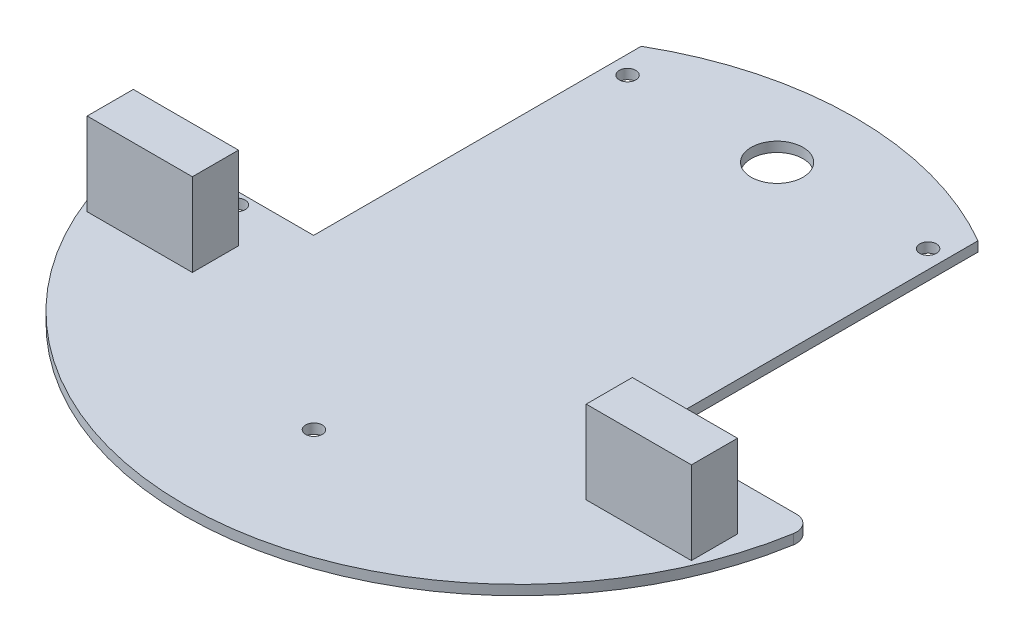
SolidWorks part; units mm, degrees
material "ABS"
ref_plane "Front Plane" through (0, 0, 0) normal (0, 0, 1) x (1, 0, 0)
ref_plane "Top Plane" through (0, 0, 0) normal (0, 1, 0) x (1, 0, 0)
ref_plane "Right Plane" through (0, 0, 0) normal (1, 0, 0) x (0, 0, -1)
sketch "Sketch1" plane through (0, 0, 0) normal (0, 1, 0) x (1, 0, 0)
  line L1 (-18, -10) -> (18, -10)
  line L2 (-18, -10) -> (-18, 10)
  line L3 (-18, 10) -> (18, 10)
  line L4 (18, -10) -> (18, 10)
  line L5 (-18, -10) -> (18, 10) construction
  line L6 (-18, 10) -> (18, -10) construction
  point P0 (0, 0)
  dimension "D1" = 36
  dimension "D2" = 20
extrude "Boss-Extrude1" add sketch "Sketch1" along normal blind 1.9
sketch "Sketch3" plane through (0, 0, 0) normal (0, -1, 0) x (1, 0, 0)
  line L0 (0, 0) -> (0, 52.4373) construction
  line L1 (37.5, -26.7252) -> (-37.5, -26.7252) construction
  line L2 (37.5, -26.7252) -> (32.5, -26.7252)
  line L3 (0, 0) -> (0, -36.2287) construction
  line L4 (-37.5, -26.7252) -> (-32.5, -26.7252)
  line L5 (32.5, -26.7252) -> (32.5, 33.2748)
  line L6 (-32.5, -26.7252) -> (-32.5, 33.2748)
  line L7 (32.5, 33.2748) -> (60.6723, 33.2748)
  line L9 (-32.5, 33.2748) -> (-60.6723, 33.2748)
  arc A0 (37.5, -26.7252) -> (-37.5, -26.7252) centre (0, 26.2187) cw
  arc A1 (-34.5855, -36.9136) -> (34.3936, -36.9136) centre (-0.0959, 26.3685) ccw construction
  arc A2 (68.1909, 19.7187) -> (51.8431, 70.9907) centre (0, 26.2187) ccw construction
  arc A3 (63.6319, 36.7654) -> (-63.6319, 36.7654) centre (0, 26.2187) ccw
  circle A4 centre (0, 26.2187) radius 72.5 construction
  arc A5 (-60.6723, 33.2748) -> (-63.6319, 36.7654) centre (-60.6723, 36.2748) cw
  arc A6 (60.6723, 33.2748) -> (63.6319, 36.7654) centre (60.6723, 36.2748) ccw
  point P7 (0, 26.2187)
  point P20 (-64.1129, 33.2748)
  point P26 (64.1129, 33.2748)
  dimension "D1" = 4
  dimension "D3" = 5
  dimension "D4" = 60
  dimension "D5" = 3
  dimension "D6" = 7.0562
  dimension "D2" = 65
extrude "Boss-Extrude2" add sketch "Sketch3" against normal blind 1.9
sketch "Sketch4" plane through (0, 1.9, 0) normal (0, 1, 0) x (1, 0, 0)
  line L0 (-32.5, 26.7252) -> (-32.5, 34.1947)
  line L1 (-32.5, 34.1947) -> (-40.4421, 34.1947)
  line L2 (-40.4421, 34.1947) -> (-37.5, 26.7252)
  line L3 (-37.5, 26.7252) -> (-32.5, 26.7252)
  line L4 (0, 0) -> (0, 49.3906) construction
  line L5 (37.5, 26.7252) -> (32.5, 26.7252)
  line L6 (40.4421, 34.1947) -> (37.5, 26.7252)
  line L7 (32.5, 34.1947) -> (40.4421, 34.1947)
  line L8 (32.5, 26.7252) -> (32.5, 34.1947)
  arc A0 (37.5, 26.7252) -> (-37.5, 26.7252) centre (0, -26.2187) ccw construction
extrude "Cut-Extrude1" cut sketch "Sketch4" against normal blind 10
sketch "Sketch5" plane through (0, 1.9, 0) normal (0, 1, 0) x (1, 0, 0)
  line L0 (0, 0) -> (0, 38.6605) construction
  circle A0 centre (0, 23.6605) radius 5
  arc A1 (32.5, 29.9334) -> (-32.5, 29.9334) centre (0, -26.2187) ccw construction
  dimension "D1" = 10
  dimension "D2" = 15
extrude "Cut-Extrude2" cut sketch "Sketch5" against normal up to surface (1.9 mm away) up to face at (0, 0, 23.8273)
sketch "Sketch6" plane through (0, 1.9, 0) normal (0, 1, 0) x (1, 0, 0)
  line L0 (0, 38.6605) -> (0, -90.7187) construction
  line L1 (-45, -35.5743) -> (45, -35.5743) construction
  line L2 (-29, 23.8048) -> (29, 23.8048) construction
  line L3 (-45, -31.5743) -> (-45, -49.6893) construction
  line L4 (-50, -31.5743) -> (-40, -31.5743) construction
  arc A0 (32.5, 29.9334) -> (-32.5, 29.9334) centre (0, -26.2187) ccw construction
  arc A1 (-63.6319, -36.7654) -> (63.6319, -36.7654) centre (0, -26.2187) ccw construction
  circle A2 centre (0, -65.7187) radius 1.6
  circle A3 centre (-45, -35.5743) radius 1.6
  circle A4 centre (45, -35.5743) radius 1.6
  circle A5 centre (-29, 23.8048) radius 1.6
  circle A6 centre (29, 23.8048) radius 1.6
  dimension "D1" = 25
  dimension "D2" = 3.2
  dimension "D3" = 4
  dimension "D5" = 58
extrude "Cut-Extrude3" cut sketch "Sketch6" against normal up to surface (1.9 mm away) up to face at (0, 0, -28.6605)
sketch "Esquisse1" plane through (0, 1.9, 0) normal (0, 1, 0) x (1, 0, 0)
  line L0 (0, 0) -> (0, -58.0938) construction
  line L1 (58.3, -42.2748) -> (38, -42.2748)
  line L2 (58.3, -42.2748) -> (58.3, -51.1748)
  line L3 (58.3, -51.1748) -> (38, -51.1748)
  line L4 (38, -42.2748) -> (38, -51.1748)
  line L5 (-38, -42.2748) -> (-38, -51.1748)
  line L6 (-58.3, -51.1748) -> (-38, -51.1748)
  line L7 (-58.3, -42.2748) -> (-58.3, -51.1748)
  line L8 (-58.3, -42.2748) -> (-38, -42.2748)
  line L10 (32.5, -33.2748) -> (60.6723, -33.2748) construction
  dimension "D1" = 20.3
  dimension "D2" = 38
  dimension "D3" = 9
  dimension "D4" = 8.9
extrude "Boss.-Extru.1" add sketch "Esquisse1" along normal blind 16
